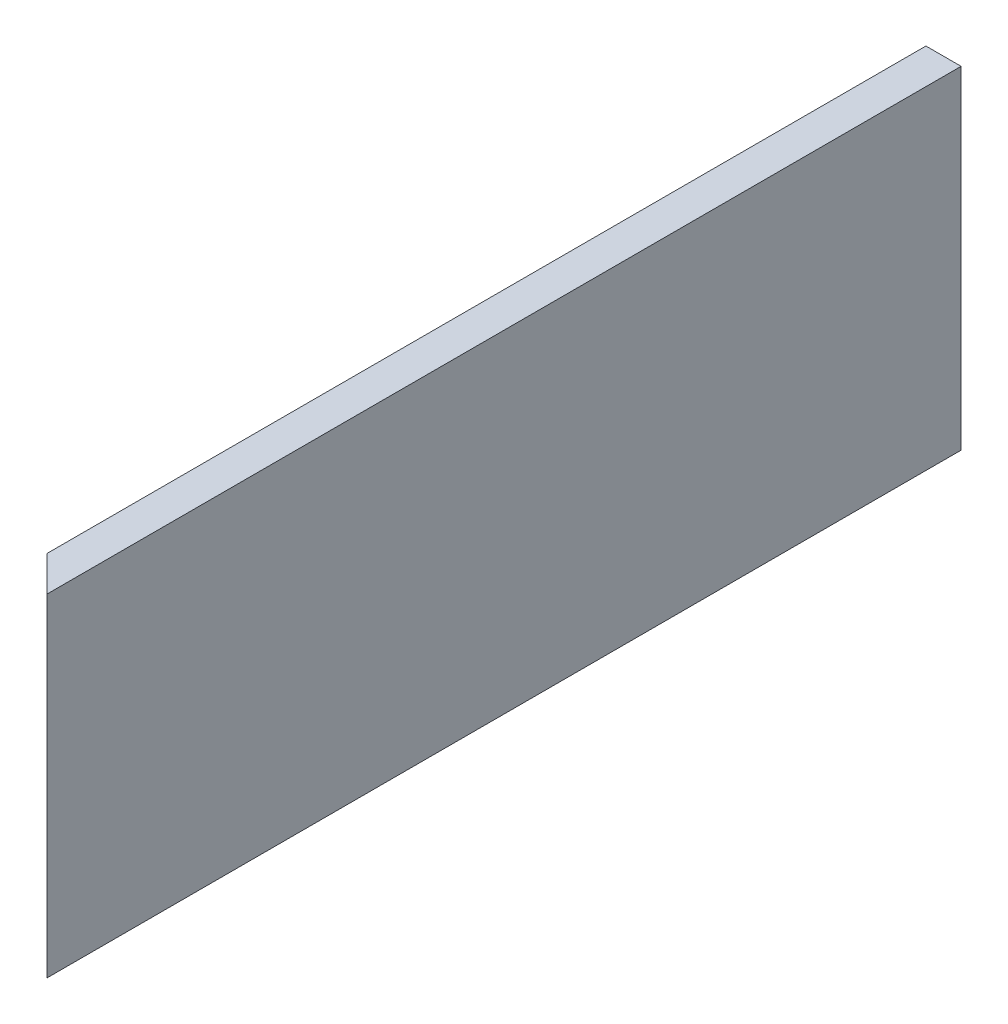
SolidWorks part; units mm, degrees
ref_plane "Front Plane" through (0, 0, 0) normal (0, 0, 1) x (1, 0, 0)
ref_plane "Top Plane" through (0, 0, 0) normal (0, 1, 0) x (1, 0, 0)
ref_plane "Right Plane" through (0, 0, 0) normal (1, 0, 0) x (0, 0, -1)
sketch "Sketch1" plane through (0, 0, 0) normal (1, 0, 0) x (0, 0, -1)
  line L1 (165, -60) -> (-165, -60)
  line L2 (165, -60) -> (165, 60)
  line L3 (165, 60) -> (-165, 60)
  line L4 (-165, -60) -> (-165, 60)
  line L5 (165, -60) -> (-165, 60) construction
  line L6 (165, 60) -> (-165, -60) construction
  point P0 (0, 0)
  dimension "D1" = 120
  dimension "D2" = 330
extrude "Boss-Extrude1" add sketch "Sketch1" along normal blind 12.7
chamfer "Chamfer1" distance 12.7 angle 45 2 edges at (0, 0, 165) (0, -60, 0)
